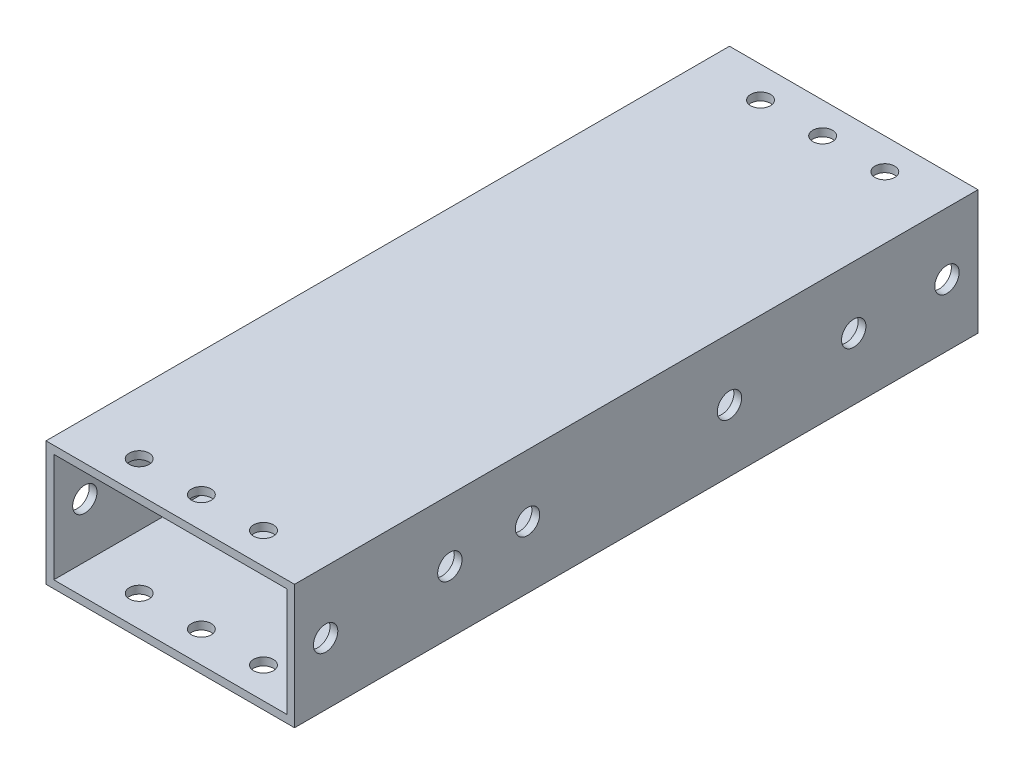
SolidWorks part; units mm, degrees
material "6061-T6 (SS)"
ref_plane "Front Plane" through (0, 0, 0) normal (0, 0, 1) x (1, 0, 0)
ref_plane "Top Plane" through (0, 0, 0) normal (0, 1, 0) x (1, 0, 0)
ref_plane "Right Plane" through (0, 0, 0) normal (1, 0, 0) x (0, 0, -1)
sketch "Sketch1" plane through (0, 0, 0) normal (0, 0, 1) x (1, 0, 0)
  line L0 (-23.8125, 11.1125) -> (23.8125, 11.1125)
  line L1 (-25.4, -12.7) -> (25.4, -12.7)
  line L2 (-25.4, -12.7) -> (-25.4, 12.7)
  line L3 (-25.4, 12.7) -> (25.4, 12.7)
  line L4 (25.4, -12.7) -> (25.4, 12.7)
  line L5 (-25.4, -12.7) -> (25.4, 12.7) construction
  line L6 (-25.4, 12.7) -> (25.4, -12.7) construction
  line L7 (23.8125, -11.1125) -> (23.8125, 11.1125)
  line L8 (-23.8125, -11.1125) -> (23.8125, -11.1125)
  line L9 (-23.8125, -11.1125) -> (-23.8125, 11.1125)
  point P0 (0, 0)
  dimension "D1" = 50.8
  dimension "D2" = 25.4
  dimension "D3" = 1.5875
extrude "Boss-Extrude1" add sketch "Sketch1" along normal mid plane 139.7
sketch "Sketch2" plane through (0, 12.7, 0) normal (0, 1, 0) x (1, 0, 0)
  line L0 (25.4, 69.85) -> (-25.4, 69.85) construction
  line L1 (25.4, 0) -> (-25.4, 0) construction
  line L2 (25.4, -69.85) -> (25.4, 69.85) construction
  line L3 (-25.4, -69.85) -> (-25.4, 69.85) construction
  circle A0 centre (-12.7, 63.5) radius 2.0193
  circle A1 centre (0, 63.5) radius 2.0193
  circle A2 centre (12.7, 63.5) radius 2.0193
  circle A3 centre (12.7, -63.5) radius 2.0193
  circle A4 centre (0, -63.5) radius 2.0193
  circle A5 centre (-12.7, -63.5) radius 2.0193
  dimension "D1" = 4.0386
  dimension "D2" = 12.7
  dimension "D3" = 12.7
  dimension "D4" = 6.35
extrude "Cut-Extrude1" cut sketch "Sketch2" against normal through all
sketch "Sketch3" plane through (25.4, 0, 0) normal (1, 0, 0) x (0, 0, -1)
  line L0 (0, 12.7) -> (0, -12.7) construction
  line L1 (-69.85, 12.7) -> (69.85, 12.7) construction
  line L2 (-69.85, -12.7) -> (69.85, -12.7) construction
  line L3 (-69.85, -12.7) -> (-69.85, 12.7) construction
  line L5 (69.85, -12.7) -> (69.85, 12.7) construction
  circle A8 centre (63.5, 0) radius 2.4892
  circle A9 centre (44.45, 0) radius 2.4892
  circle A10 centre (19.05, 0) radius 2.4892
  circle A11 centre (-63.5, 0) radius 2.4892
  circle A14 centre (-38.1, 0) radius 2.4892
  circle A15 centre (-22.225, 0) radius 2.4892
  dimension "D1" = 6.35
  dimension "D3" = 47.625
  dimension "D8" = 4.9784
  dimension "D2" = 25.4
  dimension "D6" = 19.05
  dimension "D7" = 25.4
extrude "Cut-Extrude2" cut sketch "Sketch3" against normal through all
